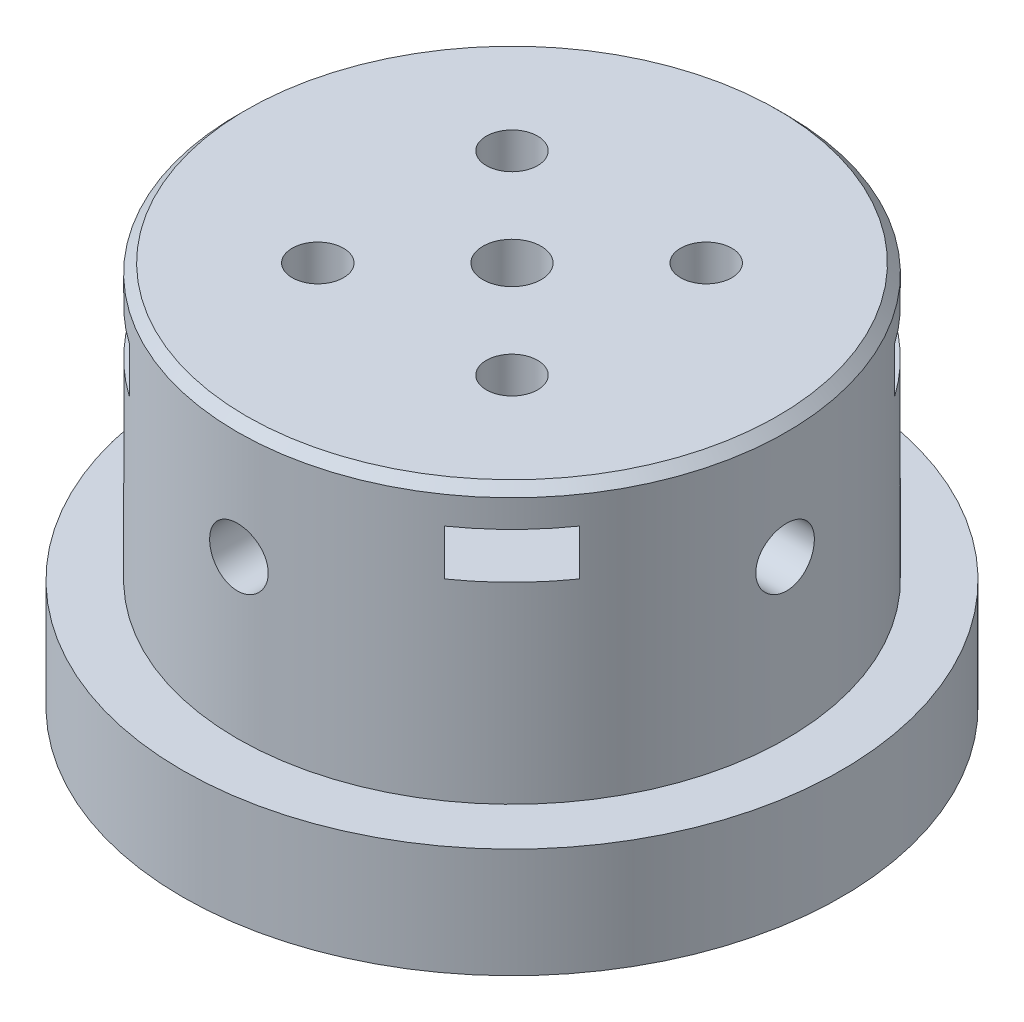
SolidWorks part; units mm, degrees
ref_plane "Front Plane" through (0, 0, 0) normal (0, 0, 1) x (1, 0, 0)
ref_plane "Top Plane" through (0, 0, 0) normal (0, 1, 0) x (1, 0, 0)
ref_plane "Right Plane" through (0, 0, 0) normal (1, 0, 0) x (0, 0, -1)
sketch "Sketch1" plane through (0, 0, 0) normal (0, 1, 0) x (1, 0, 0)
  circle A0 centre (0, 0) radius 15
  dimension "D1" = 30
extrude "Boss-Extrude1" add sketch "Sketch1" along normal blind 2
sketch "Sketch2" plane through (0, 2, 0) normal (0, 1, 0) x (1, 0, 0)
  circle A0 centre (0, 0) radius 13.5
  circle A1 centre (0, 0) radius 15
  circle A2 centre (0, 0) radius 15
  dimension "D1" = 0
  dimension "D2" = 1.5
extrude "Boss-Extrude2" add sketch "Sketch2" against normal up to surface (15 mm away)
sketch "Sketch3" plane through (0, -13, 0) normal (0, -1, 0) x (1, 0, 0)
  circle A0 centre (0, 0) radius 13.5 construction
  circle A1 centre (0, 0) radius 13.5
  circle A2 centre (0, 0) radius 18
  dimension "D1" = 36
extrude "Boss-Extrude3" add sketch "Sketch3" along normal up to surface (2 mm away)
sketch "Sketch4" plane through (0, -15, 0) normal (0, -1, 0) x (1, 0, 0)
  circle A0 centre (0, 0) radius 16.1
  circle A1 centre (0, 0) radius 18
  circle A2 centre (0, 0) radius 18
  dimension "D2" = 32.2
  dimension "D1" = 0
extrude "Boss-Extrude4" add sketch "Sketch4" along normal up to surface (3.9878 mm away)
chamfer "Chamfer1" distance 1 angle 45 1 edges at (0, -15, 13.5)
sketch "Sketch5" plane through (0, 2, 0) normal (0, 1, 0) x (1, 0, 0)
  circle A0 centre (0, 0) radius 13.5
  circle A1 centre (0, 0) radius 13.5 construction
extrude "Boss-Extrude5" add sketch "Sketch5" against normal up to surface (10.8216 mm away)
sketch "Sketch6" plane through (0, 2, 0) normal (0, 1, 0) x (1, 0, 0)
  circle A0 centre (0, 0) radius 1.5875
  dimension "D1" = 3.175
extrude "Cut-Extrude1" cut sketch "Sketch6" against normal through all both and the other way through all
sketch "Sketch7" plane through (0, 0, 0) normal (1, 0, 0) x (0, 0, -1)
  line L0 (0, 0) -> (0, -8.8216) construction
  line L1 (-1.5875, -8.8216) -> (1.5875, -8.8216) construction
  circle A0 centre (0, -4.4108) radius 1.6
  dimension "D1" = 3.2
extrude "Cut-Extrude2" cut sketch "Sketch7" against normal through all
ref_axis "Axis1" through (0, -14, 0) along (0, 1, 0)
ref_plane "Plane2" through (-10, 0, 0) normal (1, 0, 0) x (0, 0, -1)
ref_plane "Plane3" through (-9, 0, 0) normal (1, 0, 0) x (0, 0, -1)
sketch "Sketch11" plane through (-10, 0, 0) normal (1, 0, 0) x (0, 0, -1)
  circle A0 centre (0, -4.4108) radius 1.6 construction
  circle A1 centre (0, -4.4108) radius 1.6 construction
  circle A2 centre (0, -4.4108) radius 2
  dimension "D1" = 4
extrude "Cut-Extrude7" [suppressed] cut sketch "Sketch11" along normal blind 5.5
sketch "Sketch12" plane through (-10, 0, 0) normal (1, 0, 0) x (0, 0, -1)
  circle A0 centre (0, -4.4108) radius 3.5
  dimension "D1" = 7
extrude "Cut-Extrude8" [suppressed] cut sketch "Sketch12" against normal blind 5
chamfer "Chamfer2" [suppressed] distance 1 angle 45
pattern_circular "CirPattern3" count 4 over 360 about axis through (0, -14, 0) along (0, 1, 0) of "Cut-Extrude2", "Cut-Extrude7", "Cut-Extrude8", "Chamfer2"
sketch "Sketch13" plane through (-9, 0, 0) normal (1, 0, 0) x (0, 0, -1)
  line L0 (-2.75, -5.9985) -> (-2.75, -8.8216)
  line L1 (0, -7.5862) -> (2.75, -5.9985) construction
  line L2 (2.75, -5.9985) -> (2.75, -2.8231)
  line L3 (2.75, -2.8231) -> (0, -1.2354)
  line L4 (0, -1.2354) -> (-2.75, -2.8231)
  line L5 (-2.75, -2.8231) -> (-2.75, -5.9985)
  line L6 (-2.75, -5.9985) -> (0, -7.5862) construction
  line L7 (-2.75, -8.8216) -> (2.75, -8.8216)
  line L8 (2.75, -8.8216) -> (2.75, -5.9985)
  line L9 (-1.5875, -8.8216) -> (1.5875, -8.8216) construction
  circle A0 centre (0, -4.4108) radius 2.75 construction
  circle A1 centre (0, -4.4108) radius 1.6 construction
  dimension "D1" = 5.5
extrude "Cut-Extrude9" cut sketch "Sketch13" along normal blind 3
pattern_circular "CirPattern4" count 4 over 360 about axis through (0, -14, 0) along (0, 1, 0) of "Cut-Extrude9"
sketch "Sketch14" plane through (0, 2, 0) normal (0, -1, 0) x (1, 0, 0)
  line L0 (0, 0) -> (0, 13.5) construction
  line L1 (0, 0) -> (-9.5459, 9.5459) construction
  circle A0 centre (0, 0) radius 13.5 construction
  circle A1 centre (-5.3033, 5.3033) radius 1.4
  circle A2 centre (5.3033, 5.3033) radius 1.4
  circle A3 centre (5.3033, -5.3033) radius 1.4
  circle A4 centre (-5.3033, -5.3033) radius 1.4
  point P18 (0, 0)
  dimension "D3" = 2.8
  dimension "D1" = 45
  dimension "D2" = 7.5
  dimension "D4" = 4
extrude "Cut-Extrude10" cut sketch "Sketch14" along normal blind 4.5 and the other way through all
ref_plane "Plane4" through (0, 0, 0) normal (0, 1, 0) x (1, 0, 0)
sketch "Sketch15" plane through (0, 0, 0) normal (0, 1, 0) x (1, 0, 0)
  line L0 (0, 0) -> (-10.6066, 10.6066) construction
  line L1 (-8.2032, 4.5263) -> (-12.4451, 8.7681)
  line L2 (-7.4262, 7.4262) -> (-8.2032, 4.5263) construction
  line L3 (-8.2032, 4.5263) -> (-6.0803, 2.4034)
  line L4 (-6.0803, 2.4034) -> (-3.1804, 3.1804)
  line L5 (-3.1804, 3.1804) -> (-2.4034, 6.0803)
  line L6 (-2.4034, 6.0803) -> (-4.5263, 8.2032)
  line L7 (-4.5263, 8.2032) -> (-7.4262, 7.4262) construction
  line L8 (-12.4451, 8.7681) -> (-8.7681, 12.4451)
  line L9 (-8.7681, 12.4451) -> (-4.5263, 8.2032)
  line L10 (12.4451, 8.7681) -> (8.2032, 4.5263)
  line L11 (6.0803, 2.4034) -> (8.2032, 4.5263)
  line L12 (3.1804, 3.1804) -> (6.0803, 2.4034)
  line L13 (2.4034, 6.0803) -> (3.1804, 3.1804)
  line L14 (4.5263, 8.2032) -> (2.4034, 6.0803)
  line L15 (4.5263, 8.2032) -> (8.7681, 12.4451)
  line L16 (8.7681, 12.4451) -> (12.4451, 8.7681)
  line L17 (8.7681, -12.4451) -> (4.5263, -8.2032)
  line L18 (2.4034, -6.0803) -> (4.5263, -8.2032)
  line L19 (3.1804, -3.1804) -> (2.4034, -6.0803)
  line L20 (6.0803, -2.4034) -> (3.1804, -3.1804)
  line L21 (8.2032, -4.5263) -> (6.0803, -2.4034)
  line L22 (8.2032, -4.5263) -> (12.4451, -8.7681)
  line L23 (12.4451, -8.7681) -> (8.7681, -12.4451)
  line L24 (-12.4451, -8.7681) -> (-8.2032, -4.5263)
  line L25 (-6.0803, -2.4034) -> (-8.2032, -4.5263)
  line L26 (-3.1804, -3.1804) -> (-6.0803, -2.4034)
  line L27 (-2.4034, -6.0803) -> (-3.1804, -3.1804)
  line L28 (-4.5263, -8.2032) -> (-2.4034, -6.0803)
  line L29 (-4.5263, -8.2032) -> (-8.7681, -12.4451)
  line L30 (-8.7681, -12.4451) -> (-12.4451, -8.7681)
  circle A0 centre (0, 0) radius 15 construction
  circle A1 centre (-5.3033, 5.3033) radius 2.6 construction
  point P5 (-5.3033, 5.3033)
  point P41 (0, 0)
  dimension "D1" = 5.2
  dimension "D2" = 4
extrude "Cut-Extrude11" cut sketch "Sketch15" against normal blind 2.5
chamfer "Chamfer3" distance 0.5 angle 45 1 edges at (0, 2, 15)
sketch "Sketch16" plane through (0, -8.8216, 0) normal (0, -1, 0) x (1, 0, 0)
  line L0 (0, 0) -> (0, 18) construction
  line L1 (0, 0) -> (-12.7279, 12.7279) construction
  line L2 (-4.25, 4.25) -> (-4.25, 12.8136)
  line L3 (-2.75, 6) -> (-2.75, 9) construction
  line L4 (-4.25, 4.25) -> (-12.8136, 4.25)
  line L5 (4.25, 4.25) -> (12.8136, 4.25)
  line L6 (4.25, 4.25) -> (4.25, 12.8136)
  line L7 (4.25, -4.25) -> (4.25, -12.8136)
  line L8 (4.25, -4.25) -> (12.8136, -4.25)
  line L9 (-4.25, -4.25) -> (-12.8136, -4.25)
  line L10 (-4.25, -4.25) -> (-4.25, -12.8136)
  circle A0 centre (0, 0) radius 18 construction
  circle A1 centre (0, 0) radius 13.5 construction
  arc A2 (-12.8136, 4.25) -> (-4.25, 12.8136) centre (0, 0) cw
  arc A4 (4.25, 12.8136) -> (12.8136, 4.25) centre (0, 0) cw
  arc A5 (12.8136, -4.25) -> (4.25, -12.8136) centre (0, 0) cw
  arc A6 (-4.25, -12.8136) -> (-12.8136, -4.25) centre (0, 0) cw
  point P26 (0, 0)
  dimension "D1" = 45
  dimension "D2" = 1.5
  dimension "D3" = 4
extrude "Cut-Extrude12" cut sketch "Sketch16" against normal offset from surface (4.3216 mm away) 2 up to face at (-6.5434, -2.5, 6.5434)
